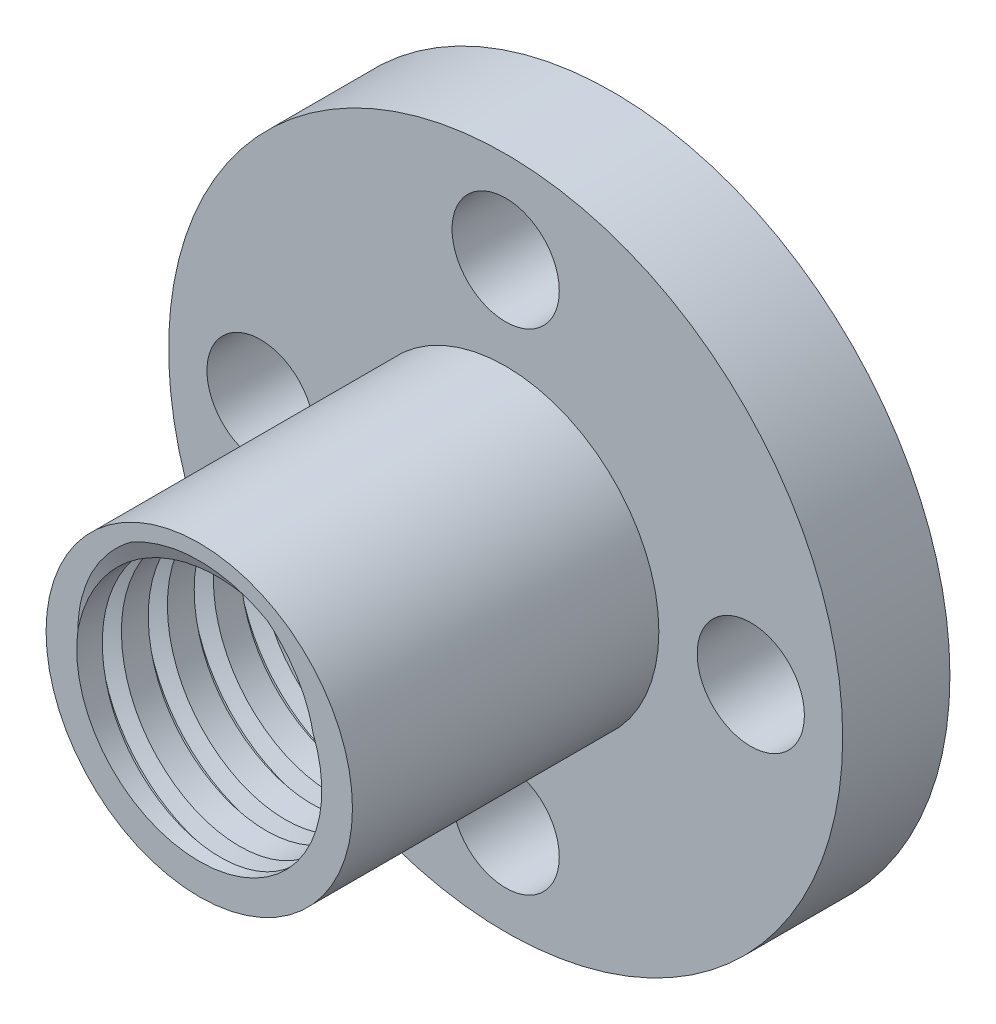
SolidWorks part; units mm, degrees
ref_plane "Front Plane" through (0, 0, 0) normal (0, 0, 1) x (1, 0, 0)
ref_plane "Top Plane" through (0, 0, 0) normal (0, 1, 0) x (1, 0, 0)
ref_plane "Right Plane" through (0, 0, 0) normal (1, 0, 0) x (0, 0, -1)
sketch "Sketch1" plane through (0, 0, 0) normal (0, 0, 1) x (1, 0, 0)
  circle A0 centre (0, 0) radius 5
  dimension "D1" = 10
extrude "Boss-Extrude1" add sketch "Sketch1" along normal blind 1.5
sketch "Sketch2" plane through (0, 0, 1.5) normal (0, 0, 1) x (1, 0, 0)
  circle A0 centre (0, 0) radius 11
  dimension "D1" = 22
extrude "Boss-Extrude2" add sketch "Sketch2" along normal blind 3.5
sketch "Sketch3" plane through (0, 0, 5) normal (0, 0, 1) x (1, 0, 0)
  circle A0 centre (0, 0) radius 5
  dimension "D1" = 10
extrude "Boss-Extrude3" add sketch "Sketch3" along normal blind 10
sketch "Sketch4" plane through (0, 0, 5) normal (0, 0, 1) x (1, 0, 0)
  circle A0 centre (0, 8) radius 1.75
  circle A1 centre (0, -8) radius 1.75
  circle A2 centre (8, 0) radius 1.75
  circle A3 centre (-8, 0) radius 1.75
  dimension "D1" = 3.5
  dimension "D2" = 3.5
  dimension "D3" = 3.5
  dimension "D4" = 3.5
  dimension "D5" = 8
  dimension "D6" = 8
  dimension "D7" = 8
  dimension "D8" = 8
extrude "Cut-Extrude1" cut sketch "Sketch4" against normal blind 4
sketch "Sketch5" plane through (0, 0, 15) normal (0, 0, 1) x (1, 0, 0)
  circle A0 centre (0, 0) radius 4
  dimension "D1" = 8
extrude "Cut-Extrude2" cut sketch "Sketch5" against normal blind 15
sketch "Sketch6" plane through (0, 0, 0) normal (1, 0, 0) x (0, 0, -1)
  line L0 (0, 0) -> (0, 6.4678) construction
  line L1 (0.5581, 3.5) -> (-0.4419, 3.5)
  line L2 (-0.4419, 3.5) -> (-0.125, 4.5)
  line L3 (-0.125, 4.5) -> (0.125, 4.5)
  line L4 (0.125, 4.5) -> (0.5581, 3.5)
  dimension "D1" = 3.5
  dimension "D2" = 0.25
  dimension "D3" = 1
  dimension "D4" = 1
  dimension "D5" = 0.125
sketch "Sketch7" plane through (0, 0, 0) normal (0, 0, -1) x (-1, 0, 0)
  circle A0 centre (0, 0) radius 5
curve "Helix/Spiral1" pitch 1.5 height 16.875 radius 5 centre (0, 0, 0) axis (0, 0, 1) start towards (1, 0, 0)
sweep "Cut-Sweep1" cut profiles "Sketch6" path "Helix/Spiral1" align with end faces yes
